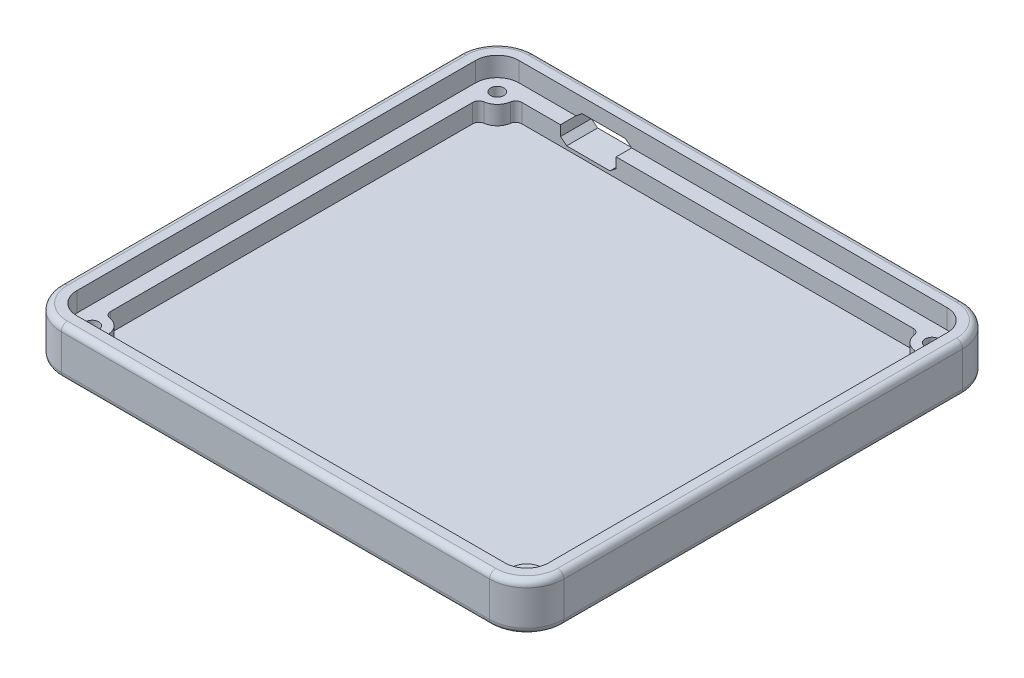
SolidWorks part; units mm, degrees
material "ABS"
ref_plane "Front Plane" through (0, 0, 0) normal (0, 0, 1) x (1, 0, 0)
ref_plane "Top Plane" through (0, 0, 0) normal (0, 1, 0) x (1, 0, 0)
ref_plane "Right Plane" through (0, 0, 0) normal (1, 0, 0) x (0, 0, -1)
sketch "Sketch2" plane through (0, 0, 0) normal (0, 1, 0) x (1, 0, 0)
  line L1 (-69.195, 71.435) -> (69.195, 71.435)
  line L2 (-76.195, 64.435) -> (-76.195, -64.435)
  line L3 (-69.195, -71.435) -> (69.195, -71.435)
  line L4 (76.195, 64.435) -> (76.195, -64.435)
  line L5 (-76.195, 71.435) -> (76.195, -71.435) construction
  line L6 (-76.195, -71.435) -> (76.195, 71.435) construction
  arc A0 (-76.195, -64.435) -> (-69.195, -71.435) centre (-69.195, -64.435) ccw
  arc A1 (-69.195, 71.435) -> (-76.195, 64.435) centre (-69.195, 64.435) ccw
  arc A2 (69.195, 71.435) -> (76.195, 64.435) centre (69.195, 64.435) cw
  arc A3 (69.195, -71.435) -> (76.195, -64.435) centre (69.195, -64.435) ccw
  point P0 (0, 0)
  dimension "D3" = 7
  dimension "D1" = 152.39
  dimension "D2" = 142.87
extrude "Boss-Extrude2" add sketch "Sketch2" along normal blind 3
sketch "Sketch3" plane through (0, 3, 0) normal (0, 1, 0) x (1, 0, 0)
  line L0 (-69.195, -71.435) -> (69.195, -71.435) construction
  line L1 (76.195, -64.435) -> (76.195, 64.435) construction
  line L2 (69.195, 71.435) -> (-69.195, 71.435) construction
  line L3 (-76.195, 64.435) -> (-76.195, -64.435) construction
  line L4 (-69.195, -71.435) -> (69.195, -71.435)
  line L5 (76.195, -64.435) -> (76.195, 64.435)
  line L6 (69.195, 71.435) -> (-69.195, 71.435)
  line L7 (-76.195, 64.435) -> (-76.195, -64.435)
  line L8 (0, -80.5945) -> (0, 82.9206) construction
  line L9 (9.041, 0) -> (-113.0904, 0) construction
  line L10 (-81.195, 64.435) -> (-81.195, -64.435)
  line L11 (-69.195, -76.435) -> (69.195, -76.435)
  line L12 (81.195, -64.435) -> (81.195, 64.435)
  line L13 (69.195, 76.435) -> (-69.195, 76.435)
  line L14 (-71.195, 60.44) -> (-71.195, -60.44)
  line L15 (-65.2, -66.435) -> (65.2, -66.435)
  line L16 (71.195, -60.44) -> (71.195, 60.44)
  line L17 (65.2, 66.435) -> (-65.2, 66.435)
  line L18 (-71.195, 60.44) -> (-70.195, 60.44)
  line L19 (-65.2, 66.435) -> (-65.2, 65.435)
  line L20 (-71.195, 64.435) -> (-71.195, -64.435) construction
  line L21 (69.195, 66.435) -> (-69.195, 66.435) construction
  line L22 (65.2, 66.435) -> (65.2, 65.435)
  line L23 (71.195, 60.44) -> (70.195, 60.44)
  line L24 (65.2, -66.435) -> (65.2, -65.435)
  line L25 (71.195, -60.44) -> (70.195, -60.44)
  line L26 (-65.2, -66.435) -> (-65.2, -65.435)
  line L27 (-71.195, -60.44) -> (-70.195, -60.44)
  line L28 (-69.195, -66.435) -> (69.195, -66.435) construction
  line L29 (71.195, -64.435) -> (71.195, 64.435) construction
  arc A0 (-76.195, -64.435) -> (-69.195, -71.435) centre (-69.195, -64.435) ccw construction
  arc A1 (69.195, -71.435) -> (76.195, -64.435) centre (69.195, -64.435) ccw construction
  arc A2 (76.195, 64.435) -> (69.195, 71.435) centre (69.195, 64.435) ccw construction
  arc A3 (-69.195, 71.435) -> (-76.195, 64.435) centre (-69.195, 64.435) ccw construction
  arc A4 (-76.195, -64.435) -> (-69.195, -71.435) centre (-69.195, -64.435) ccw
  arc A5 (69.195, -71.435) -> (76.195, -64.435) centre (69.195, -64.435) ccw
  arc A6 (76.195, 64.435) -> (69.195, 71.435) centre (69.195, 64.435) ccw
  arc A7 (-69.195, 71.435) -> (-76.195, 64.435) centre (-69.195, 64.435) ccw
  circle A9 centre (-70.2, -65.44) radius 2.15
  circle A10 centre (70.2, -65.44) radius 2.15
  circle A11 centre (70.2, 65.44) radius 2.15
  circle A12 centre (-70.2, 65.44) radius 2.15
  arc A13 (-81.195, -64.435) -> (-69.195, -76.435) centre (-69.195, -64.435) ccw
  arc A14 (69.195, -76.435) -> (81.195, -64.435) centre (69.195, -64.435) ccw
  arc A15 (81.195, 64.435) -> (69.195, 76.435) centre (69.195, 64.435) ccw
  arc A16 (-69.195, 76.435) -> (-81.195, 64.435) centre (-69.195, 64.435) ccw
  arc A21 (-70.195, 60.44) -> (-65.2, 65.435) centre (-70.195, 65.435) ccw
  arc A22 (70.195, 60.44) -> (65.2, 65.435) centre (70.195, 65.435) cw
  arc A23 (-69.195, 66.435) -> (-71.195, 64.435) centre (-69.195, 64.435) ccw construction
  arc A24 (70.195, -60.44) -> (65.2, -65.435) centre (70.195, -65.435) ccw
  arc A25 (-70.195, -60.44) -> (-65.2, -65.435) centre (-70.195, -65.435) cw
  arc A26 (-71.195, -64.435) -> (-69.195, -66.435) centre (-69.195, -64.435) ccw construction
  arc A27 (69.195, -66.435) -> (71.195, -64.435) centre (69.195, -64.435) ccw construction
  arc A28 (71.195, 64.435) -> (69.195, 66.435) centre (69.195, 64.435) ccw construction
  arc M10 (-76.195, -64.435) -> (-69.195, -71.435) centre (-69.195, -64.435) ccw
  line M11 (-69.195, -71.435) -> (69.195, -71.435)
  arc M12 (69.195, -71.435) -> (76.195, -64.435) centre (69.195, -64.435) ccw
  line M13 (76.195, -64.435) -> (76.195, 64.435)
  arc M14 (76.195, 64.435) -> (69.195, 71.435) centre (69.195, 64.435) ccw
  line M15 (69.195, 71.435) -> (-69.195, 71.435)
  arc M16 (-69.195, 71.435) -> (-76.195, 64.435) centre (-69.195, 64.435) ccw
  line M17 (-76.195, 64.435) -> (-76.195, -64.435)
  dimension "D1" = 65.44
  dimension "D2" = 4.3
  dimension "D3" = 70.2
  dimension "D4" = 5
  dimension "D6" = 1
  dimension "D7" = 5
  dimension "D8" = 1
  dimension "D9" = 5
  dimension "D5" = 5
extrude "Boss-Extrude3" add sketch "Sketch3" along normal blind 6 and the other way blind 3 contours L13 A16 L10 A13 L11 A14 L12 A15 M10 M17 M16 M15 M14 M13 M12 M11 | L17 L16 L15 L14 M17 M10 M11 M12 M13 M14 M15 M16 region at (-72.6677, 3, 67.9077) region at (-76.1033, 3, -71.3433)
sketch "Sketch8" plane through (0, 9, 0) normal (0, 1, 0) x (1, 0, 0)
  line L0 (-69.195, -76.435) -> (69.195, -76.435) construction
  line L1 (81.195, -64.435) -> (81.195, 64.435) construction
  line L2 (69.195, 76.435) -> (-69.195, 76.435) construction
  line L3 (-81.195, 64.435) -> (-81.195, -64.435) construction
  line L4 (76.195, -64.435) -> (76.195, 64.435)
  line L5 (69.195, 71.435) -> (-69.195, 71.435)
  line L6 (-76.195, 64.435) -> (-76.195, -64.435)
  line L7 (-69.195, -71.435) -> (69.195, -71.435)
  line L8 (76.195, -64.435) -> (76.195, 64.435)
  line L9 (69.195, 71.435) -> (-69.195, 71.435)
  line L10 (-76.195, 64.435) -> (-76.195, -64.435)
  line L11 (-69.195, -71.435) -> (69.195, -71.435)
  line L12 (-69.195, -76.435) -> (69.195, -76.435)
  line L13 (81.195, -64.435) -> (81.195, 64.435)
  line L14 (69.195, 76.435) -> (-69.195, 76.435)
  line L15 (-81.195, 64.435) -> (-81.195, -64.435)
  line L16 (-76.195, 64.435) -> (-76.195, -64.435)
  line L17 (-69.195, -71.435) -> (69.195, -71.435)
  line L18 (76.195, -64.435) -> (76.195, 64.435)
  line L19 (69.195, 71.435) -> (-69.195, 71.435)
  arc A0 (-81.195, -64.435) -> (-69.195, -76.435) centre (-69.195, -64.435) ccw construction
  arc A1 (69.195, -76.435) -> (81.195, -64.435) centre (69.195, -64.435) ccw construction
  arc A2 (81.195, 64.435) -> (69.195, 76.435) centre (69.195, 64.435) ccw construction
  arc A3 (-69.195, 76.435) -> (-81.195, 64.435) centre (-69.195, 64.435) ccw construction
  arc A4 (76.195, 64.435) -> (69.195, 71.435) centre (69.195, 64.435) ccw
  arc A5 (-69.195, 71.435) -> (-76.195, 64.435) centre (-69.195, 64.435) ccw
  arc A6 (-76.195, -64.435) -> (-69.195, -71.435) centre (-69.195, -64.435) ccw
  arc A7 (69.195, -71.435) -> (76.195, -64.435) centre (69.195, -64.435) ccw
  arc A8 (76.195, 64.435) -> (69.195, 71.435) centre (69.195, 64.435) ccw
  arc A9 (-69.195, 71.435) -> (-76.195, 64.435) centre (-69.195, 64.435) ccw
  arc A10 (-76.195, -64.435) -> (-69.195, -71.435) centre (-69.195, -64.435) ccw
  arc A11 (69.195, -71.435) -> (76.195, -64.435) centre (69.195, -64.435) ccw
  arc A12 (-81.195, -64.435) -> (-69.195, -76.435) centre (-69.195, -64.435) ccw
  arc A13 (69.195, -76.435) -> (81.195, -64.435) centre (69.195, -64.435) ccw
  arc A14 (81.195, 64.435) -> (69.195, 76.435) centre (69.195, 64.435) ccw
  arc A15 (-69.195, 76.435) -> (-81.195, 64.435) centre (-69.195, 64.435) ccw
  arc A16 (-76.195, -64.435) -> (-69.195, -71.435) centre (-69.195, -64.435) ccw
  arc A17 (69.195, -71.435) -> (76.195, -64.435) centre (69.195, -64.435) ccw
  arc A18 (76.195, 64.435) -> (69.195, 71.435) centre (69.195, 64.435) ccw
  arc A19 (-69.195, 71.435) -> (-76.195, 64.435) centre (-69.195, 64.435) ccw
  line M17 (69.195, 76.435) -> (-69.195, 76.435)
  arc M18 (-69.195, 76.435) -> (-81.195, 64.435) centre (-69.195, 64.435) ccw
  line M19 (-81.195, 64.435) -> (-81.195, -64.435)
  arc M20 (-81.195, -64.435) -> (-69.195, -76.435) centre (-69.195, -64.435) ccw
  line M21 (-69.195, -76.435) -> (69.195, -76.435)
  arc M22 (69.195, -76.435) -> (81.195, -64.435) centre (69.195, -64.435) ccw
  line M23 (81.195, -64.435) -> (81.195, 64.435)
  arc M24 (81.195, 64.435) -> (69.195, 76.435) centre (69.195, 64.435) ccw
  dimension "D1" = 0
  dimension "D2" = 5
extrude "Boss-Extrude4" add sketch "Sketch8" along normal blind 6.28 contours A11 L11 A10 L10 A9 L9 A8 L8 M24 M17 M18 M19 M20 M21 M22 M23 region at (-76.1033, 9, 71.3433)
sketch "Sketch9" plane through (0, 0, -76.435) normal (0, 0, -1) x (-1, 0, 0)
  line L0 (81.195, 0) -> (81.195, 15.28) construction
  line L7 (48.775, 10.605) -> (34.775, 10.605)
  line L8 (34.775, 10.605) -> (32.775, 9.005)
  line L14 (50.775, 9.005) -> (48.775, 10.605)
  line L15 (54.9775, 7.345) -> (29.0731, 7.345) construction
  line L16 (32.775, 9.005) -> (32.775, 5.685)
  line L17 (50.775, 9.005) -> (50.775, 5.685)
  line L18 (41.775, 10.605) -> (41.775, 5.8424) construction
  line L19 (-69.195, 0) -> (69.195, 0) construction
  line L20 (50.775, 5.685) -> (48.775, 4.085)
  line L21 (48.775, 4.085) -> (34.775, 4.085)
  line L22 (34.775, 4.085) -> (32.775, 5.685)
  point P7 (50.775, 7.345)
  point P20 (32.775, 7.345)
  dimension "D2" = 7.345
  dimension "D1" = 39.42
  dimension "D5" = 3.26
  dimension "D6" = 1.66
  dimension "D7" = 18
  dimension "D8" = 14
extrude "Cut-Extrude1" cut sketch "Sketch9" against normal blind 10
fillet "Fillet1" radius 2 8 edges at (-65.2, 6, -66.435) (-71.195, 6, -60.44) (-71.195, 6, 60.44) (-65.2, 6, 66.435) (71.195, 6, 60.44) (65.2, 6, 66.435) (65.2, 6, -66.435) (71.195, 6, -60.44)
sketch "Sketch11" plane through (0, 3, 0) normal (0, 1, 0) x (1, 0, 0)
  circle A0 centre (-70.2, 65.44) radius 2.15
  circle A1 centre (70.2, 65.44) radius 2.15
  circle A2 centre (70.2, -65.4964) radius 2.15
  circle A3 centre (-70.2, -65.44) radius 2.15
  dimension "D1" = 4.3
  dimension "D2" = 4.3
  dimension "D3" = 4.3
  dimension "D4" = 4.3
extrude "Cut-Extrude3" cut sketch "Sketch11" against normal through all both and the other way through all contours A3 | A2 | A1 | A0 region at (-70.2, 3, -65.44) region at (70.2, 3, -65.44) region at (70.2, 3, 65.4964) region at (-70.2, 3, 65.44)
sketch "Sketch10" plane through (0, 0, 0) normal (0, -1, 0) x (1, 0, 0)
  line L0 (0, -76.435) -> (0, 105.632) construction
  line L1 (69.195, -76.435) -> (-69.195, -76.435) construction
  line L2 (-81.195, 0) -> (91.4068, 0) construction
  line L3 (-81.195, -64.435) -> (-81.195, 64.435) construction
  line L4 (68.1793, 61.94) -> (66.1585, 65.44)
  line L5 (-66.1585, 65.44) -> (-68.1793, 68.94)
  line L6 (-68.1793, 68.94) -> (-72.2207, 68.94)
  line L7 (-72.2207, 68.94) -> (-74.2415, 65.44)
  line L8 (-74.2415, 65.44) -> (-72.2207, 61.94)
  line L9 (-72.2207, 61.94) -> (-68.1793, 61.94)
  line L10 (-68.1793, 61.94) -> (-66.1585, 65.44)
  line L11 (72.2207, 61.94) -> (68.1793, 61.94)
  line L12 (74.2415, 65.44) -> (72.2207, 61.94)
  line L13 (72.2207, 68.94) -> (74.2415, 65.44)
  line L14 (68.1793, 68.94) -> (72.2207, 68.94)
  line L15 (66.1585, 65.44) -> (68.1793, 68.94)
  line L16 (72.2207, -61.94) -> (68.1793, -61.94)
  line L17 (74.2415, -65.44) -> (72.2207, -61.94)
  line L18 (72.2207, -68.94) -> (74.2415, -65.44)
  line L19 (68.1793, -68.94) -> (72.2207, -68.94)
  line L20 (66.1585, -65.44) -> (68.1793, -68.94)
  line L21 (68.1793, -61.94) -> (66.1585, -65.44)
  line L22 (-68.1793, -61.94) -> (-66.1585, -65.44)
  line L23 (-72.2207, -61.94) -> (-68.1793, -61.94)
  line L24 (-74.2415, -65.44) -> (-72.2207, -61.94)
  line L25 (-72.2207, -68.94) -> (-74.2415, -65.44)
  line L26 (-68.1793, -68.94) -> (-72.2207, -68.94)
  line L27 (-66.1585, -65.44) -> (-68.1793, -68.94)
  line L28 (-70.2, 65.44) -> (-62.8389, 65.44)
  circle A0 centre (-70.2, 65.44) radius 3.5 construction
  circle A1 centre (-70.2, 65.44) radius 2.15 construction
  dimension "D3" = 7
extrude "Cut-Extrude2" cut sketch "Sketch10" against normal blind 4 contours L9 L10 L5 L6 L7 L8 | L12 L11 L4 L15 L14 L13 | L22 L27 L26 L25 L24 L23 | L17 L16 L21 L20 L19 L18 region at (-67.2615, 0, 63.7435)
fillet "Fillet4" radius 2 16 edges at (-77.6803, 0, -72.9203) (0, 0, -76.435) (77.6803, 0, -72.9203) (81.195, 0, 0) (77.6803, 0, 72.9203) (0, 0, 76.435) (-77.6803, 0, 72.9203) (-77.6803, 15.28, -72.9203) (0, 15.28, -76.435) (77.6803, 15.28, -72.9203) (81.195, 15.28, 0) (77.6803, 15.28, 72.9203) (0, 15.28, 76.435) (-77.6803, 15.28, 72.9203) (-81.195, 0, 0) (-81.195, 15.28, 0)
sketch "Sketch13" plane through (0, 0, 0) normal (0, -1, 0) x (1, 0, 0)
  line L0 (0, 15.661) -> (0, -101.1595) construction
  line L1 (-15, -31.435) -> (15, -31.435) construction
  line L2 (-15, -25.435) -> (15, -25.435)
  line L3 (-15, -37.435) -> (15, -37.435)
  line L4 (69.195, -76.435) -> (-69.195, -76.435) construction
  arc A0 (-15, -25.435) -> (-15, -37.435) centre (-15, -31.435) ccw
  arc A1 (15, -37.435) -> (15, -25.435) centre (15, -31.435) ccw
  point P5 (0, -31.435)
  dimension "D1" = 30
  dimension "D2" = 45
  dimension "D3" = 12
extrude "Cut-Extrude5" cut sketch "Sketch13" against normal blind 2
sketch "Sketch14" plane through (0, 0, 0) normal (0, -1, 0) x (1, 0, 0)
  line L0 (0, 20.3696) -> (0, -82.809) construction
  line L1 (69.195, -76.435) -> (-69.195, -76.435) construction
  circle A0 centre (-55, -56.435) radius 10
  circle A1 centre (55, -56.435) radius 10
  dimension "D3" = 20
  dimension "D1" = 55
  dimension "D2" = 20
extrude "Cut-Extrude6" cut sketch "Sketch14" against normal blind 2
